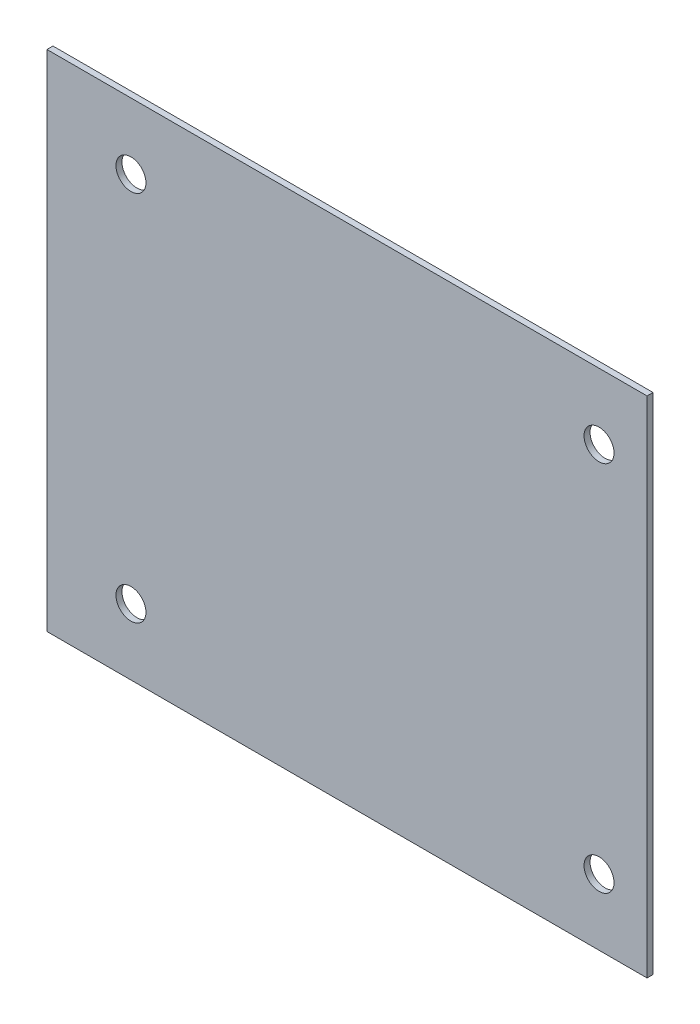
SolidWorks part; units mm, degrees
ref_plane "Front Plane" through (0, 0, 0) normal (0, 0, 1) x (1, 0, 0)
ref_plane "Top Plane" through (0, 0, 0) normal (0, 1, 0) x (1, 0, 0)
ref_plane "Right Plane" through (0, 0, 0) normal (1, 0, 0) x (0, 0, -1)
sketch "Sketch1" plane through (0, 0, 0) normal (0, 0, 1) x (1, 0, 0)
  line L1 (50, -42) -> (-50, -42)
  line L2 (50, -42) -> (50, 42)
  line L3 (50, 42) -> (-50, 42)
  line L4 (-50, -42) -> (-50, 42)
  line L5 (50, -42) -> (-50, 42) construction
  line L6 (50, 42) -> (-50, -42) construction
  line L7 (42, -31) -> (-36, -31)
  line L8 (42, -31) -> (42, 31)
  line L9 (42, 31) -> (-36, 31)
  line L10 (-36, -31) -> (-36, 31)
  line L11 (42, -31) -> (-36, 31) construction
  line L12 (42, 31) -> (-36, -31) construction
  circle A0 centre (-36, 31) radius 2.5
  circle A1 centre (42, 31) radius 2.5
  circle A2 centre (42, -31) radius 2.5
  circle A3 centre (-36, -31) radius 2.5
  point P0 (0, 0)
  point P6 (3, 0)
  dimension "D6" = 5
  dimension "D5" = 8
  dimension "D1" = 84
  dimension "D2" = 100
  dimension "D3" = 62
  dimension "D4" = 78
extrude "Boss-Extrude1" add sketch "Sketch1" along normal blind 1 contours L4 L1 L2 L3 A3 L10 A0 L9 A1 L8 A2 L7 | A3 L7 A2 L8 A1 L9 A0 L10 region at (0, -40.694, 0) region at (3, 0, 0)
